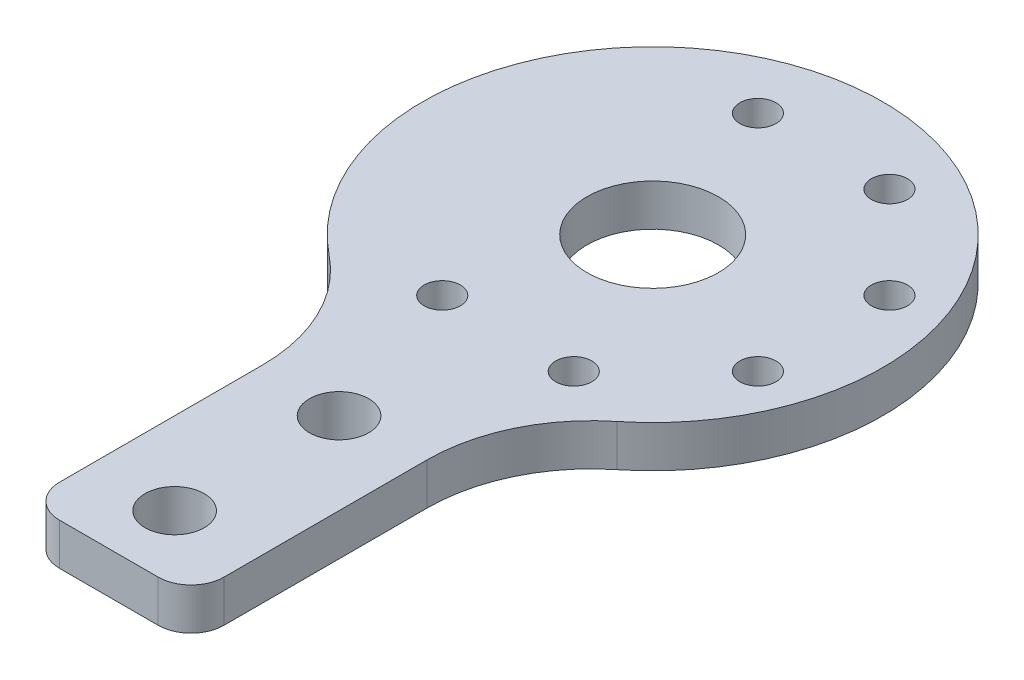
SolidWorks part; units mm, degrees
material "1060 Alloy"
ref_plane "Front Plane" through (0, 0, 0) normal (0, 0, 1) x (1, 0, 0)
ref_plane "Top Plane" through (0, 0, 0) normal (0, 1, 0) x (1, 0, 0)
ref_plane "Right Plane" through (0, 0, 0) normal (1, 0, 0) x (0, 0, -1)
sketch "Sketch1" plane through (0, 0, 0) normal (0, 1, 0) x (1, 0, 0)
  line L0 (-12.5, -82.6917) -> (12.5, -82.6917)
  line L1 (12.5, -82.6917) -> (12.5, -32.6917)
  line L2 (-12.5, -82.6917) -> (-12.5, -32.6917)
  arc A0 (12.5, -32.6917) -> (-12.5, -32.6917) centre (0, 0) ccw
  point P5 (0, -82.6917)
  dimension "D2" = 70
  dimension "D1" = 25
  dimension "D3" = 50
extrude "Boss-Extrude1" add sketch "Sketch1" along normal blind 6.35 contours A0 L2 L0 L1
sketch "Sketch2" plane through (0, 0, 0) normal (0, -1, 0) x (1, 0, 0)
  line L0 (55, 0) -> (-55, 0) construction
  point P2 (0, 0)
  point P5 (-8, 24)
  point P13 (12, 24)
  point P14 (26, 10)
  point P22 (26, -10)
  point P23 (12, -24)
  point P24 (-8, -24)
  dimension "D2" = 26
  dimension "D1" = 8
  dimension "D3" = 20
  dimension "D4" = 10
  dimension "D5" = 24
sketch "Sketch5" plane through (0, 0, 0) normal (0, -1, 0) x (1, 0, 0)
  circle A0 centre (0, 0) radius 10
  dimension "D1" = 20
extrude "Cut-Extrude1" cut sketch "Sketch5" against normal through all
sketch "Sketch6" plane through (0, 0, 0) normal (0, -1, 0) x (1, 0, 0)
  line L0 (0, 82.6917) -> (0, 47.6917) construction
  line L1 (-12.5, 82.6917) -> (12.5, 82.6917) construction
  point P5 (0, 72.6917)
  dimension "D1" = 25
  dimension "D2" = 10
hole_wizard "M8 Clearance Hole1" positions "Sketch7" profile "Sketch8" hole size "M8" standard "ANSI Metric" end condition through all
sketch "Sketch7" plane through (0, 0, 0) normal (0, -1, 0) x (-1, 0, 0)
  point P0 (0, -47.6917)
  point P3 (0, -72.6917)
sketch "Sketch8" plane through (0, 0, 47.6917) normal (1, 0, 0) x (0, 0, -1)
  line L0 (0, 0) -> (0, 6.35)
  line L1 (0, 6.35) -> (4.5, 6.35)
  line L2 (4.5, 6.35) -> (4.5, 0)
  line L5 (4.5, 0) -> (0, 0)
  line L11 (0, -6.35) -> (0, 107.95) construction
  dimension "Thru Hole Dia." = 9
  dimension "Thru Hole Depth" = 6.35
fillet "Fillet1" radius 25 2 edges at (-12.5, 3.175, 32.6917) (12.5, 3.175, 32.6917)
hole_wizard "M5 Clearance Hole1" positions "Sketch9" profile "Sketch10" hole size "M5" standard "ANSI Metric" end condition through all
sketch "Sketch9" plane through (0, 0, 0) normal (0, -1, 0) x (-1, 0, 0)
  point P18 (-12, 24)
  point P21 (8, 24)
  point P27 (-26, 10)
  point P30 (-26, -10)
  point P33 (-12, -24)
  point P36 (8, -24)
sketch "Sketch10" plane through (12, 0, -24) normal (1, 0, 0) x (0, 0, -1)
  line L0 (0, 0) -> (0, 6.35)
  line L1 (0, 6.35) -> (2.75, 6.35)
  line L2 (2.75, 6.35) -> (2.75, 0.025)
  line L3 (2.75, 0.025) -> (2.775, 0)
  line L5 (2.775, 0) -> (0, 0)
  line L6 (-2.75, 0.025) -> (-2.775, 0) construction
  line L11 (0, -6.35) -> (0, 107.95) construction
  dimension "Thru Hole Dia." = 5.5
  dimension "Thru Hole Depth" = 6.35
  dimension "Near C'Sink Dia." = 5.55
  dimension "Near C'Sink Angle" = 90
fillet "Fillet2" radius 5 2 edges at (-12.5, 3.175, 82.6917) (12.5, 3.175, 82.6917)
